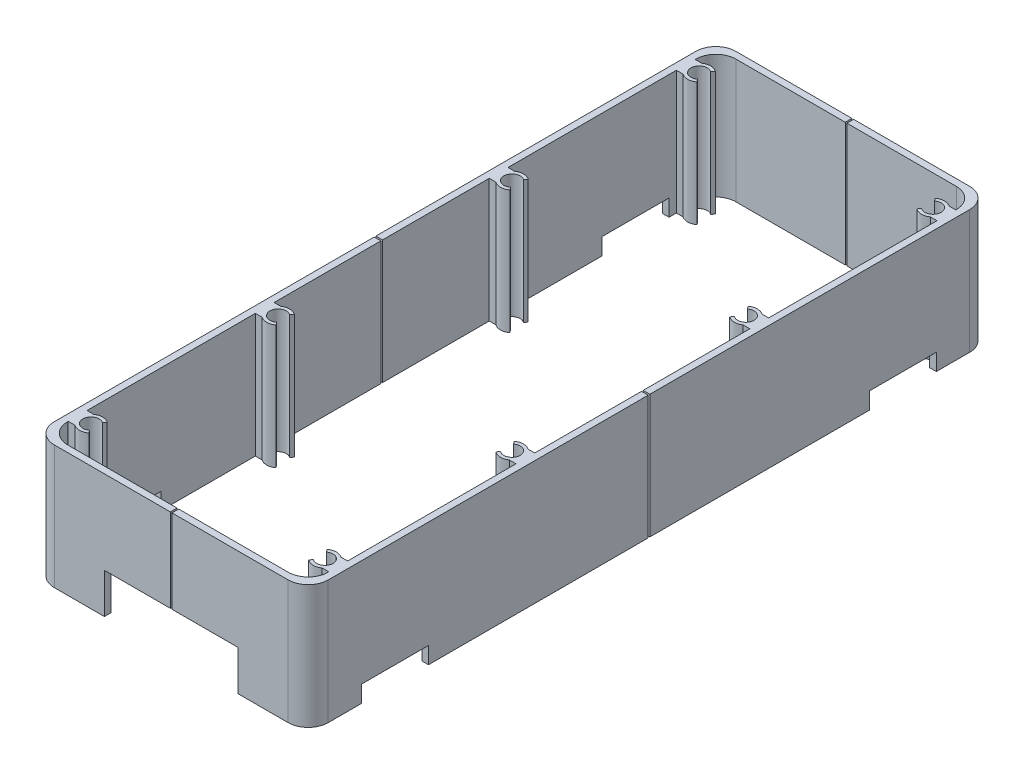
SolidWorks part; units mm, degrees
ref_plane "Спереди" through (0, 0, 0) normal (0, 0, 1) x (1, 0, 0)
ref_plane "Сверху" through (0, 0, 0) normal (0, 1, 0) x (1, 0, 0)
ref_plane "Справа" through (0, 0, 0) normal (1, 0, 0) x (0, 0, -1)
sketch "Эскиз1" plane through (0, 0, 0) normal (0, 1, 0) x (1, 0, 0)
  line L0 (-1028.5807, 0) -> (50400.4542, 0) construction
  line L1 (0, -1031.7856) -> (0, 50397.2493) construction
  line L2 (-39, 93.8111) -> (-37, 93.8111)
  line L3 (40, -101) -> (-40, -101) construction
  line L4 (40, -101) -> (40, 101) construction
  line L5 (40, 101) -> (-40, 101) construction
  line L6 (-40, -101) -> (-40, 101) construction
  line L7 (40, -101) -> (-40, 101) construction
  line L8 (40, 101) -> (-40, -101) construction
  line L9 (-35, 102) -> (-0.25, 102)
  line L10 (-41, 96) -> (-41, 0.25)
  line L11 (-35, -102) -> (-0.25, -102)
  line L12 (41, 96) -> (41, 0.25)
  line L13 (-33, 100) -> (-0.25, 100)
  line L14 (-39, 94) -> (-39, 93.8111)
  line L15 (-33, -100) -> (-0.25, -100)
  line L16 (39, 94) -> (39, 93.8111)
  line L17 (-39, 88.1889) -> (-37, 88.1889)
  line L18 (-37.45, 91) -> (-31.55, 91) construction
  line L19 (-33.5085, 92.9437) -> (-32.8998, 93.7371)
  line L20 (-33.5085, 89.0563) -> (-32.8998, 88.2629)
  line L21 (41, -0.25) -> (39, -0.25)
  line L23 (-0.25, 102) -> (-0.25, 100)
  line L25 (0.25, 102) -> (0.25, 100)
  line L26 (-41, 0.25) -> (-39, 0.25)
  line L28 (-41, -0.25) -> (-39, -0.25)
  line L29 (41, 0.25) -> (39, 0.25)
  line L30 (-39, 88.1889) -> (-39, 37.8111)
  line L31 (0.25, 100) -> (33, 100)
  line L32 (0.25, 102) -> (35, 102)
  line L33 (41, -0.25) -> (41, -96)
  line L34 (39, -0.25) -> (39, -32.1889)
  line L35 (-39, -0.25) -> (-39, -32.1889)
  line L36 (-41, -0.25) -> (-41, -96)
  line L37 (0.25, -102) -> (0.25, -100)
  line L38 (-0.25, -102) -> (-0.25, -100)
  line L39 (0.25, -102) -> (35, -102)
  line L40 (0.25, -100) -> (33, -100)
  line L45 (-1009.0774, 63) -> (48990.9226, 63) construction
  line L46 (-39, 32.1889) -> (-39, 0.25)
  line L47 (-37.45, 35) -> (-31.55, 35) construction
  line L48 (-39, 37.8111) -> (-37, 37.8111)
  line L49 (-39, 32.1889) -> (-37, 32.1889)
  line L50 (-33.5085, 33.0563) -> (-32.8998, 32.2629)
  line L51 (-33.5085, 36.9437) -> (-32.8998, 37.7371)
  line L53 (39, 88.1889) -> (39, 37.8111)
  line L54 (39, 32.1889) -> (39, 0.25)
  line L68 (39, 88.1889) -> (37, 88.1889)
  line L69 (33.5085, 89.0563) -> (32.8998, 88.2629)
  line L70 (33.5085, 92.9437) -> (32.8998, 93.7371)
  line L71 (39, 93.8111) -> (37, 93.8111)
  line L72 (33.5085, 36.9437) -> (32.8998, 37.7371)
  line L73 (39, 37.8111) -> (37, 37.8111)
  line L74 (39, 32.1889) -> (37, 32.1889)
  line L75 (33.5085, 33.0563) -> (32.8998, 32.2629)
  line L92 (-39, -88.1889) -> (-37, -88.1889)
  line L93 (-33.5085, -89.0563) -> (-32.8998, -88.2629)
  line L94 (-33.5085, -92.9437) -> (-32.8998, -93.7371)
  line L95 (-39, -93.8111) -> (-37, -93.8111)
  line L96 (39, -93.8111) -> (37, -93.8111)
  line L97 (33.5085, -92.9437) -> (32.8998, -93.7371)
  line L98 (33.5085, -89.0563) -> (32.8998, -88.2629)
  line L99 (39, -88.1889) -> (37, -88.1889)
  line L100 (39, -37.8111) -> (37, -37.8111)
  line L101 (33.5085, -36.9437) -> (32.8998, -37.7371)
  line L102 (33.5085, -33.0563) -> (32.8998, -32.2629)
  line L103 (39, -32.1889) -> (37, -32.1889)
  line L104 (-33.5085, -33.0563) -> (-32.8998, -32.2629)
  line L105 (-39, -32.1889) -> (-37, -32.1889)
  line L106 (-33.5085, -36.9437) -> (-32.8998, -37.7371)
  line L107 (-39, -37.8111) -> (-37, -37.8111)
  line L108 (-39, -37.8111) -> (-39, -88.1889)
  line L109 (-39, -93.8111) -> (-39, -94)
  line L110 (39, -93.8111) -> (39, -94)
  line L111 (39, -37.8111) -> (39, -88.1889)
  arc A0 (35, -102) -> (41, -96) centre (35, -96) ccw
  arc A1 (33, -100) -> (39, -94) centre (33, -94) ccw
  arc A2 (-41, -96) -> (-35, -102) centre (-35, -96) ccw
  arc A3 (-39, -94) -> (-33, -100) centre (-33, -94) ccw
  arc A4 (35, 102) -> (41, 96) centre (35, 96) cw
  arc A5 (33, 100) -> (39, 94) centre (33, 94) cw
  arc A6 (-35, 102) -> (-41, 96) centre (-35, 96) ccw
  arc A7 (-33, 100) -> (-39, 94) centre (-33, 94) ccw
  arc A8 (-33.5085, 92.9437) -> (-33.5085, 89.0563) centre (-35, 91) ccw
  arc A9 (-32.8998, 93.7371) -> (-37, 93.8111) centre (-35, 91) ccw
  arc A10 (-37, 88.1889) -> (-32.8998, 88.2629) centre (-35, 91) ccw
  circle A11 centre (-35, 91) radius 3.45 construction
  circle A15 centre (-35, 35) radius 3.45 construction
  arc A16 (-32.8998, 32.2629) -> (-37, 32.1889) centre (-35, 35) cw
  arc A17 (-33.5085, 33.0563) -> (-33.5085, 36.9437) centre (-35, 35) cw
  arc A18 (-37, 37.8111) -> (-32.8998, 37.7371) centre (-35, 35) cw
  circle A19 centre (-35, 35) radius 2.45 construction
  arc A28 (37, 88.1889) -> (32.8998, 88.2629) centre (35, 91) cw
  arc A29 (33.5085, 92.9437) -> (33.5085, 89.0563) centre (35, 91) cw
  arc A30 (32.8998, 93.7371) -> (37, 93.8111) centre (35, 91) cw
  arc A31 (37, 37.8111) -> (32.8998, 37.7371) centre (35, 35) ccw
  arc A32 (33.5085, 33.0563) -> (33.5085, 36.9437) centre (35, 35) ccw
  arc A33 (32.8998, 32.2629) -> (37, 32.1889) centre (35, 35) ccw
  arc A46 (-37, -88.1889) -> (-32.8998, -88.2629) centre (-35, -91) cw
  arc A47 (-33.5085, -92.9437) -> (-33.5085, -89.0563) centre (-35, -91) cw
  arc A48 (-32.8998, -93.7371) -> (-37, -93.8111) centre (-35, -91) cw
  arc A49 (32.8998, -93.7371) -> (37, -93.8111) centre (35, -91) ccw
  arc A50 (33.5085, -92.9437) -> (33.5085, -89.0563) centre (35, -91) ccw
  arc A51 (37, -88.1889) -> (32.8998, -88.2629) centre (35, -91) ccw
  arc A52 (37, -37.8111) -> (32.8998, -37.7371) centre (35, -35) cw
  arc A53 (33.5085, -33.0563) -> (33.5085, -36.9437) centre (35, -35) cw
  arc A54 (32.8998, -32.2629) -> (37, -32.1889) centre (35, -35) cw
  arc A55 (-32.8998, -32.2629) -> (-37, -32.1889) centre (-35, -35) ccw
  arc A56 (-33.5085, -33.0563) -> (-33.5085, -36.9437) centre (-35, -35) ccw
  arc A57 (-37, -37.8111) -> (-32.8998, -37.7371) centre (-35, -35) ccw
  point P4 (0, 0)
  point P26 (41, -102)
  point P29 (39, -100)
  point P32 (-41, -102)
  point P35 (-39, -100)
  point P38 (41, 102)
  point P41 (39, 100)
  point P53 (-35, 35)
  point P78 (-39, 63)
  dimension "D5" = 6
  dimension "D6" = 6.9
  dimension "D7" = 4.9
  dimension "D1" = 80
  dimension "D2" = 202
  dimension "D3" = 1
  dimension "D4" = 1
  dimension "D8" = 10
  dimension "D9" = 5
  dimension "D10" = 2
  dimension "D11" = 105
  dimension "D12" = 0.5
  dimension "D13" = 0.5
  dimension "D14" = 1
  dimension "D15" = 35
extrude "Бобышка-Вытянуть2" add sketch "Эскиз1" along normal mid plane 37 contours L10 L26 L46 L49 A16 L50 A17 L51 A18 L48 L30 L17 A10 L20 A8 L19 A9 L2 L14 A7 L13 L23 L9 A6 | L35 L105 A55 L104 A56 L106 A57 L107 L108 L92 A46 L93 A47 L94 A48 L95 L109 A3 L15 L38 L11 A2 L36 L28 | L32 A4 L12 L29 L54 L74 A33 L75 A32 L72 A31 L73 L53 L68 A28 L69 A29 L70 A30 L71 L16 A5 L31 L25 | L34 L103 A54 L102 A53 L101 A52 L100 L111 L99 A51 L98 A50 L97 A49 L96 L110 A1 L40 L37 L39 A0 L33 L21
sketch "Эскиз2" plane through (0, 0, 0) normal (0, 0, 1) x (1, 0, 0)
  line L0 (-1000.25, 0) -> (48999.75, 0) construction
  line L1 (-5, 18.5) -> (5, 18.5)
  line L2 (-5, 18.5) -> (-5, 13.5)
  line L3 (-5, 13.5) -> (5, 13.5)
  line L4 (5, 18.5) -> (5, 13.5)
  line L5 (-12.5, -9.5) -> (12.5, -9.5)
  line L6 (-12.5, -9.5) -> (-12.5, -18.5)
  line L7 (-12.5, -18.5) -> (12.5, -18.5)
  line L8 (12.5, -9.5) -> (12.5, -18.5)
  line L9 (-0.25, 18.5) -> (-0.25, -18.5) construction
  line L10 (0, -1000) -> (0, 49000) construction
  line L11 (0.25, -18.5) -> (35, -18.5) construction
  line L12 (0.25, 18.5) -> (35, 18.5) construction
  point P13 (-0.25, 0)
  dimension "D1" = 9
  dimension "D2" = 25
  dimension "D3" = 10
  dimension "D4" = 5
extrude "Вырез-Вытянуть1" [suppressed] cut sketch "Эскиз2" against normal through all from surface
sketch "Эскиз3" plane through (0, 0, 0) normal (0, 0, 1) x (1, 0, 0)
  line L0 (-1000, 0) -> (49000, 0) construction
  line L1 (0, -1000) -> (0, 49000) construction
  line L2 (-35, -18.5) -> (-0.25, -18.5) construction
  line L3 (-20, -6.5) -> (20, -6.5)
  line L4 (-20, -6.5) -> (-20, -18.5)
  line L5 (-20, -18.5) -> (20, -18.5)
  line L6 (20, -6.5) -> (20, -18.5)
  dimension "D1" = 40
  dimension "D2" = 12
extrude "Вырез-Вытянуть2" cut sketch "Эскиз3" along normal through all from surface starting at face at (-16.625, 0, 100)
sketch "Эскиз4" plane through (0, 0, 0) normal (1, 0, 0) x (0, 0, -1)
  line L0 (-1000, 0) -> (49000, 0) construction
  line L1 (0, -1000) -> (0, 49000) construction
  line L2 (-96, 18.5) -> (-96, -18.5) construction
  line L3 (-86, -13.5) -> (-66, -13.5)
  line L4 (-86, -13.5) -> (-86, -18.5)
  line L5 (-86, -18.5) -> (-66, -18.5)
  line L6 (-66, -13.5) -> (-66, -18.5)
  line L7 (-0.25, -18.5) -> (-96, -18.5) construction
  line L8 (86, -18.5) -> (66, -18.5)
  line L9 (66, -13.5) -> (66, -18.5)
  line L10 (86, -13.5) -> (66, -13.5)
  line L11 (86, -13.5) -> (86, -18.5)
  dimension "D1" = 20
  dimension "D2" = 5
  dimension "D3" = 10
extrude "Вырез-Вытянуть3" cut sketch "Эскиз4" against normal through all both and the other way through all
